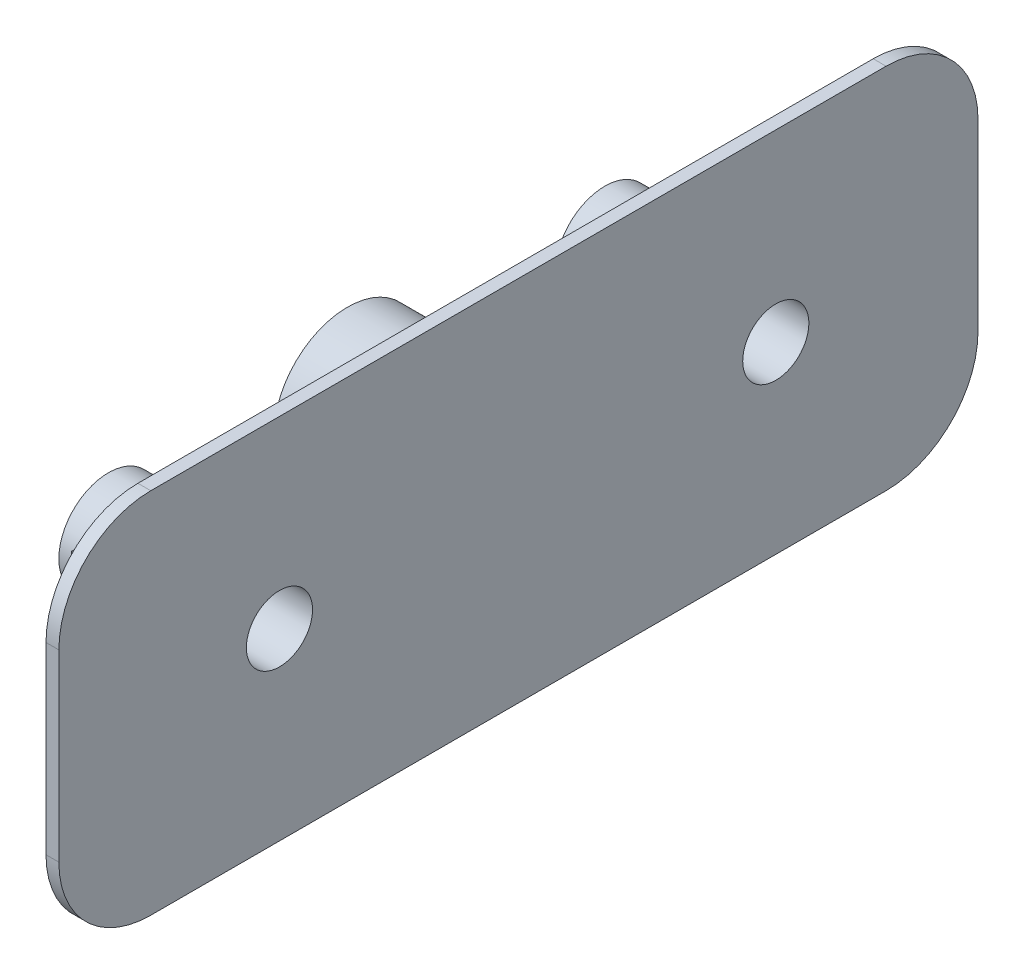
SolidWorks part; units mm, degrees
ref_plane "Front Plane" through (0, 0, 0) normal (0, 0, 1) x (1, 0, 0)
ref_plane "Top Plane" through (0, 0, 0) normal (0, 1, 0) x (1, 0, 0)
ref_plane "Right Plane" through (0, 0, 0) normal (1, 0, 0) x (0, 0, -1)
sketch "Sketch1" plane through (0, 0, 0) normal (1, 0, 0) x (0, 0, -1)
  circle A0 centre (0, 0) radius 3
  circle A2 centre (0, 0) radius 4
  dimension "D1" = 6
  dimension "D2" = 8
extrude "Boss-Extrude1" add sketch "Sketch1" along normal blind 5
sketch "Sketch2" plane through (5, 0, 0) normal (1, 0, 0) x (0, 0, -1)
  line L1 (-20, -5) -> (20, -5)
  line L2 (-20, -5) -> (-20, 5)
  line L3 (-20, 5) -> (20, 5)
  line L4 (20, -5) -> (20, 5)
  line L5 (-20, -5) -> (20, 5) construction
  line L6 (-20, 5) -> (20, -5) construction
  circle A0 centre (0, 0) radius 3
  point P0 (0, 0)
  dimension "D1" = 10
  dimension "D2" = 40
extrude "Boss-Extrude2" add sketch "Sketch2" along normal blind 3.6
sketch "Sketch7" plane through (8.6, 0, 0) normal (1, 0, 0) x (0, 0, -1)
  line L1 (25, -10) -> (-25, -10)
  line L2 (25, -10) -> (25, 10)
  line L3 (25, 10) -> (-25, 10)
  line L4 (-25, -10) -> (-25, 10)
  line L5 (25, -10) -> (-25, 10) construction
  line L6 (25, 10) -> (-25, -10) construction
  point P0 (0, 0)
  dimension "D1" = 50
  dimension "D2" = 20
extrude "Boss-Extrude3" add sketch "Sketch7" along normal blind 0.7
hole_wizard "M3 Clearance Hole1" positions "Sketch5" profile "Sketch6" hole size "M3" standard "ANSI Metric"
sketch "Sketch5" plane through (5, 0, 0) normal (-1, 0, 0) x (0, 0, 1)
  point P0 (-14, 0)
  point P2 (13, 0)
  dimension "D1" = 14
  dimension "D2" = 13
sketch "Sketch6" plane through (5, 0, -14) normal (0, 1, 0) x (0, 0, 1)
  line L0 (0, 0) -> (0, 13.0815)
  line L1 (0, 13.0815) -> (1.8, 12)
  line L2 (1.8, 12) -> (1.8, 0)
  line L5 (1.8, 0) -> (0, 0)
  line L10 (0, 13.0815) -> (-1.8, 12) construction
  line L11 (0, -6.35) -> (0, 107.95) construction
  dimension "Hole Dia." = 3.6
  dimension "Hole Depth" = 12
  dimension "Drill Angle" = 118
sketch "Sketch8" plane through (5, 0, 0) normal (-1, 0, 0) x (0, 0, 1)
  circle A0 centre (-14, 0) radius 1.8
  circle A1 centre (-14, 0) radius 2.7
  circle A2 centre (13, 0) radius 1.8
  circle A3 centre (13, 0) radius 2.7
  circle A4 centre (-14, 0) radius 1.8 construction
  circle A5 centre (13, 0) radius 1.8 construction
  dimension "D1" = 5.4
  dimension "D2" = 5.4
extrude "Boss-Extrude4" add sketch "Sketch8" along normal blind 5
fillet "Fillet2" radius 5 4 edges at (8.95, 10, -25) (8.95, -10, -25) (8.95, -10, 25) (8.95, 10, 25)
